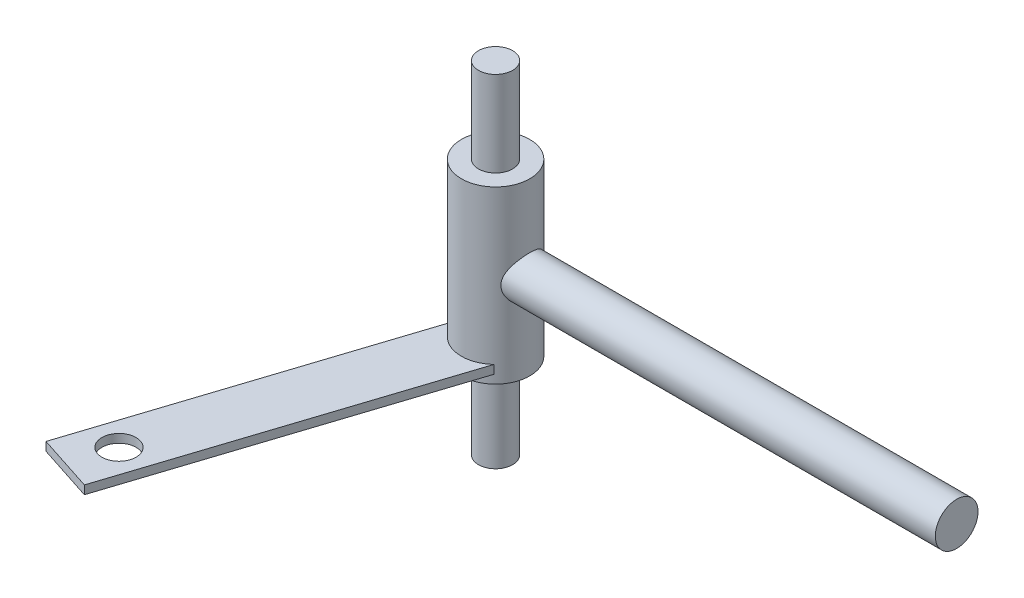
SolidWorks part; units mm, degrees
ref_plane "Front Plane" through (0, 0, 0) normal (0, 0, 1) x (1, 0, 0)
ref_plane "Top Plane" through (0, 0, 0) normal (0, 1, 0) x (1, 0, 0)
ref_plane "Right Plane" through (0, 0, 0) normal (1, 0, 0) x (0, 0, -1)
sketch "Sketch1" plane through (0, 0, 0) normal (0, 1, 0) x (1, 0, 0)
  circle A0 centre (0, 0) radius 4
  dimension "D1" = 8
extrude "Boss-Extrude1" add sketch "Sketch1" along normal mid plane 80
ref_axis "Axis1" through (0, 40, 0) along (0, -1, 0)
ref_plane "Plane1" through (0, 0, 0) normal (-0.309, 0, 0.9511) x (0, -1, 0)
sketch "Sketch3" plane through (0, 0, 0) normal (0, 1, 0) x (1, 0, 0)
  circle A0 centre (0, 0) radius 8
  dimension "D1" = 16
extrude "Boss-Extrude2" add sketch "Sketch3" along normal mid plane 40
sketch "Sketch4" plane through (0, 0, 0) normal (1, 0, 0) x (0, 0, -1)
  circle A0 centre (0, 0) radius 5
  dimension "D1" = 10
extrude "Boss-Extrude3" add sketch "Sketch4" along normal blind 108
sketch "Sketch5" plane through (0, 0, 0) normal (-0.309, 0, 0.9511) x (0.9511, 0, 0.309)
  line L0 (-8, -20) -> (8, -20) construction
  line L5 (-7, -16) -> (7, -16)
  line L6 (-7, -16) -> (-7, -18)
  line L7 (-7, -18) -> (7, -18)
  line L8 (7, -16) -> (7, -18)
  line L9 (-7, -16) -> (7, -18) construction
  line L10 (-7, -18) -> (7, -16) construction
  point P0 (0, -17)
  dimension "D1" = 14
  dimension "D2" = 2
  dimension "D3" = 2
extrude "Boss-Extrude4" add sketch "Sketch5" along normal blind 80
sketch "Sketch6" plane through (0, -16, 0) normal (0, 1, 0) x (1, 0, 0)
  line L0 (-18.064, -78.2476) -> (-31.3788, -73.9214) construction
  line L1 (-18.064, -78.2476) -> (5.4606, -5.8465) construction
  circle A0 centre (-21.6312, -66.574) radius 4
  dimension "D1" = 8
  dimension "D2" = 10
  dimension "D3" = 7
extrude "Cut-Extrude1" cut sketch "Sketch6" against normal up to next
